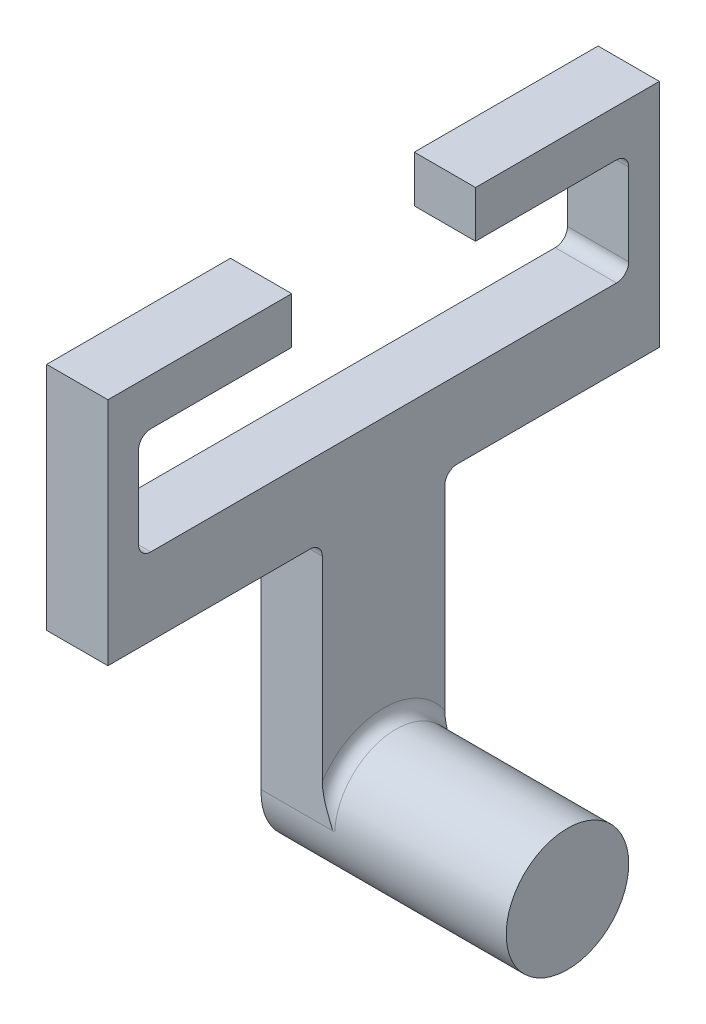
SolidWorks part; units mm, degrees
material "6061-T6 (SS)"
ref_plane "Front Plane" through (0, 0, 0) normal (0, 0, 1) x (1, 0, 0)
ref_plane "Top Plane" through (0, 0, 0) normal (0, 1, 0) x (1, 0, 0)
ref_plane "Right Plane" through (0, 0, 0) normal (1, 0, 0) x (0, 0, -1)
sketch "Sketch2" plane through (0, 0, 0) normal (1, 0, 0) x (0, 0, -1)
  circle A0 centre (0, 0) radius 12.7
  dimension "D1" = 25.4
extrude "Boss-Extrude1" add sketch "Sketch2" along normal blind 50.8 contours A0
sketch "Sketch3" plane through (0, 0, 0) normal (-1, 0, 0) x (0, 0, 1)
  line L1 (-12.6854, 0.6087) -> (12.7146, 0.6087)
  line L2 (-12.6854, 0.6087) -> (-12.6854, 51.4087)
  line L3 (-12.6854, 51.4087) -> (12.7146, 51.4087)
  line L4 (12.7146, 0.6087) -> (12.7146, 51.4087)
  circle A0 centre (0, 0) radius 12.7 construction
  dimension "D1" = 25.4
  dimension "D2" = 50.8
extrude "Boss-Extrude2" add sketch "Sketch3" against normal blind 12.7
sketch "Sketch5" plane through (0, 0, 0) normal (1, 0, 0) x (0, 0, -1)
  line L1 (50.8, 67.3933) -> (-50.8, 67.3933)
  line L2 (50.8, 67.3933) -> (50.8, 51.3913)
  line L3 (50.8, 51.3913) -> (-50.8, 51.3913)
  line L4 (-50.8, 67.3933) -> (-50.8, 51.3913)
  line L5 (50.8, 67.3933) -> (-50.8, 51.3913) construction
  line L6 (50.8, 51.3913) -> (-50.8, 67.3933) construction
  point P0 (0, 59.3923)
  dimension "D1" = 101.6
  dimension "D2" = 16.002
extrude "Boss-Extrude3" add sketch "Sketch5" along normal blind 12.7 separate body
sketch "Sketch6" plane through (0, 0, 0) normal (1, 0, 0) x (0, 0, -1)
  line L1 (-50.8, 51.3913) -> (-57.15, 51.3913)
  line L2 (-50.8, 51.3913) -> (-50.8, 89.4913)
  line L3 (-50.8, 89.4913) -> (-57.15, 89.4913)
  line L4 (-57.15, 51.3913) -> (-57.15, 89.4913)
  line L5 (50.8, 51.3913) -> (57.15, 51.3913)
  line L6 (50.8, 51.3913) -> (50.8, 89.4913)
  line L7 (50.8, 89.4913) -> (57.15, 89.4913)
  line L8 (57.15, 51.3913) -> (57.15, 89.4913)
  dimension "D1" = 6.35
  dimension "D2" = 38.1
  dimension "D3" = 6.35
  dimension "D4" = 38.1
extrude "Boss-Extrude4" add sketch "Sketch6" along normal blind 12.7
sketch "Sketch7" plane through (0, 0, 0) normal (1, 0, 0) x (0, 0, -1)
  line L1 (-57.15, 89.4913) -> (-19.05, 89.4913)
  line L2 (-57.15, 89.4913) -> (-57.15, 99.1433)
  line L3 (-57.15, 99.1433) -> (-19.05, 99.1433)
  line L4 (-19.05, 89.4913) -> (-19.05, 99.1433)
  line L5 (57.15, 89.4913) -> (19.05, 89.4913)
  line L6 (57.15, 89.4913) -> (57.15, 99.1433)
  line L7 (57.15, 99.1433) -> (19.05, 99.1433)
  line L8 (19.05, 89.4913) -> (19.05, 99.1433)
  dimension "D1" = 38.1
  dimension "D2" = 38.1
  dimension "D3" = 9.652
  dimension "D4" = 9.652
extrude "Boss-Extrude5" add sketch "Sketch7" along normal blind 12.7
combine bodies "Combine1" operation type add bodies to combine 102 105
fillet "Fillet1" radius 2.54 7 edges at (6.35, 51.3913, 12.7146) (6.35, 51.3913, -12.6854) (12.7, 12.7, 0) (6.35, 89.4913, -50.8) (6.35, 67.3933, -50.8) (6.35, 89.4913, 50.8) (6.35, 67.3933, 50.8)
equation "\"d_A\"= 1.00in"
equation "\"t_B\"= 0.50in"
equation "\"h_B\"= 2.00in"
equation "\"h_C\"= 0.625in"
equation "\"L_C\"= 4.00in"
equation "\"L_D\"= 1.500in"
equation "\"h_E\"= 0.375in"
equation "\"L_E\"= 1.500in"
equation "\"W_B\"= \"d_A\""
equation "\"L_A\"= 2.00in"
equation "\"t_C\"= \"t_B\""
equation "\"t_D\"= \"t_B\""
equation "\"t_E\"= \"t_B\""
